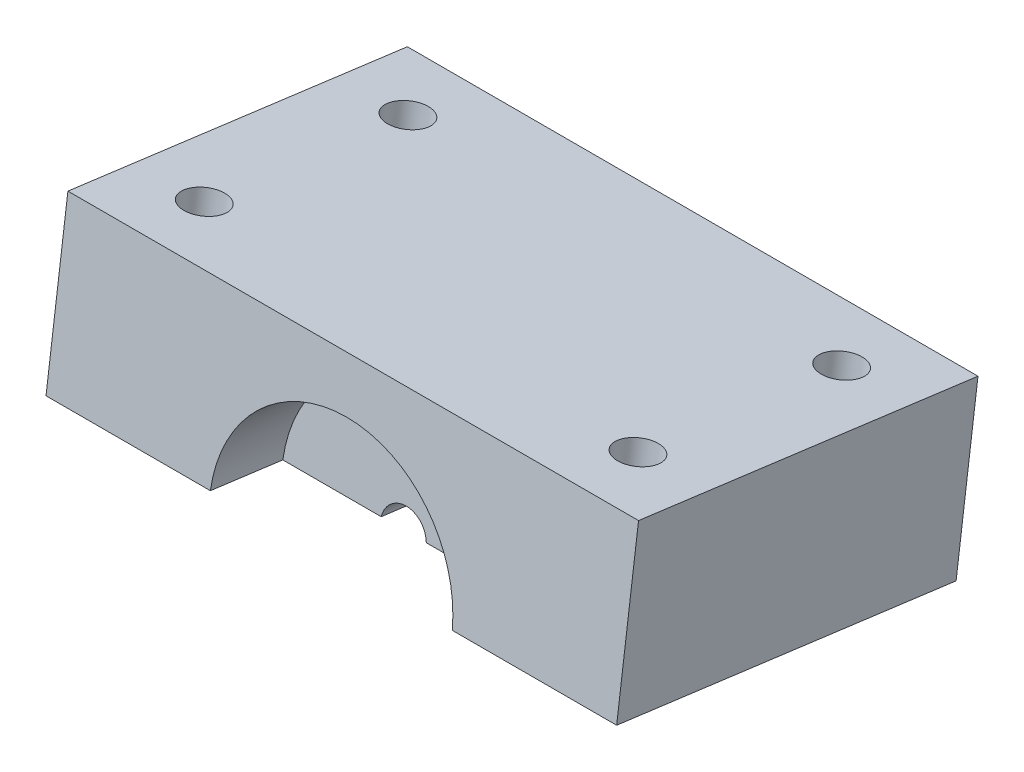
SolidWorks part; units mm, degrees
ref_plane "Front Plane" through (0, 0, 0) normal (0, 0, 1) x (1, 0, 0)
ref_plane "Top Plane" through (0, 0, 0) normal (0, 1, 0) x (1, 0, 0)
ref_plane "Right Plane" through (0, 0, 0) normal (1, 0, 0) x (0, 0, -1)
ref_axis "Axis1" through (-88.99, 0, 0) along (1, 0, 0)
ref_plane "7.5deg Ref" through (0, 0, 0) normal (0, 0.1305, 0.9914) x (1, 0, 0)
sketch "Sketch1" plane through (0, 0, 0) normal (0, 0.1305, 0.9914) x (1, 0, 0)
  line L1 (62.5, 0.75) -> (62.5, 37.5)
  line L2 (62.5, 37.5) -> (-62.5, 37.5)
  line L3 (-62.5, 37.5) -> (-62.5, 0.75)
  line L4 (-62.5, 0.75) -> (-26.4894, 0.75)
  line L5 (26.4894, 0.75) -> (62.5, 0.75)
  line L6 (0, 0) -> (0, 37.5) construction
  arc A0 (26.4894, 0.75) -> (-26.4894, 0.75) centre (0, 0) ccw
  dimension "D3" = 53
  dimension "D1" = 125
  dimension "D2" = 36.75
  dimension "D4" = 0.75
extrude "Extrude Top Block" add sketch "Sketch1" against normal blind 75
sketch "Sketch2" plane through (0, 37.1792, -4.8947) normal (0, 0.9914, -0.1305) x (1, 0, 0)
  line L0 (0, 75.0939) -> (0, -22.75) construction
  line L1 (0, -25.4238) -> (0, 25.4238) construction
  line L2 (-72.1929, 37.5) -> (74.8374, 37.5) construction
  line L3 (-47.5, 59.9553) -> (-47.5, 15) construction
  line L4 (-62.5, 75) -> (-62.5, 0) construction
  line L5 (-59.8697, 0) -> (59.8697, 0) construction
  circle A0 centre (-47.5, 15) radius 2.75
  circle A1 centre (-47.5, 60) radius 2.75
  circle A2 centre (47.5, 15) radius 2.75
  circle A3 centre (47.5, 60) radius 2.75
  dimension "D3" = 5.5
  dimension "D1" = 15
  dimension "D2" = 15
  dimension "D4" = 37.5
extrude "Cut-Extrude Bolt Pattern" cut sketch "Sketch2" against normal through all both and the other way through all
sketch "Sketch4" plane through (0, 0, 0) normal (0, 0.1305, 0.9914) x (1, 0, 0)
  line L0 (-26.4894, 0.75) -> (26.4894, 0.75)
  arc A0 (26.4894, 0.75) -> (-26.4894, 0.75) centre (0, 0) ccw
  arc A1 (26.4894, 0.75) -> (-26.4894, 0.75) centre (0, 0) ccw construction
extrude "Extrude Addition Material" add sketch "Sketch4" along direction (0, 0.1305, 0.9914) on the side against the normal up to surface (75 mm away) from offset 16 up to face at (0, 7.3543, -76.6154) offset against normal yes
sketch "Sketch3" plane through (0, 0, 0) normal (1, 0, 0) x (0, 0, -1)
  line L0 (0, 0) -> (74.2659, -9.7773) construction
  line L1 (21.9059, 43.8111) -> (14.9673, -8.8927) construction
  line L2 (41.4977, 1.0928) -> (61.3266, -1.5177)
  line L3 (74.4563, -9.0459) -> (0.0979, 0.7436) construction
  line L13 (61.3266, -1.5177) -> (60.4781, -7.9621)
  line L14 (60.4781, -7.9621) -> (40.6492, -5.3516)
  line L15 (40.6492, -5.3516) -> (41.4977, 1.0928)
  line L16 (74.4563, -9.0459) -> (79.2531, 27.3897) construction
  line L17 (40.6492, -5.3516) -> (46.6434, 40.1787) construction
  line L18 (7.8146, 59.3575) -> (-7.8146, -59.3575) construction
  dimension "D1" = 0.75
  dimension "D2" = 20
  dimension "D6" = 6.5
  dimension "D7" = 16
  dimension "D8" = 25
revolve "Cut-Extrude Seat for Linear Bearing" cut sketch "Sketch3" angle 360 about L0
sketch "Sketch6" plane through (0, -2.0884, -15.8631) normal (0, 0.1305, 0.9914) x (1, 0, 0)
  line L1 (-4.9434, 0.75) -> (4.9434, 0.75)
  line L3 (-26.4894, 0.75) -> (26.4894, 0.75) construction
  arc A0 (4.9434, 0.75) -> (-4.9434, 0.75) centre (0, 0) ccw
  arc A1 (26.4894, 0.75) -> (-26.4894, 0.75) centre (0, 0) ccw construction
  dimension "D1" = 10
extrude "Cut-Extrude Shaft Pathway" cut sketch "Sketch6" against normal up to surface (59 mm away) up to face at (0, 9.1719, -76.8547)
sketch "Sketch7" plane through (0, -9.7895, -74.3584) normal (0, -0.1305, -0.9914) x (-1, 0, 0)
  line L0 (0, 66.1064) -> (0, -24.2487) construction
  line L1 (0, 25.4238) -> (0, -25.4238) construction
  line L2 (-20, 20) -> (20, 20) construction
  circle A0 centre (-20, 20) radius 2
  circle A1 centre (20, 20) radius 2
  dimension "D4" = 4
  dimension "D5" = 4
  dimension "D1" = 20
  dimension "D2" = 20
  dimension "D3" = 20
extrude "Cut-Extrude1" cut sketch "Sketch7" against normal blind 25
sketch "Sketch8" plane through (0, 37.1792, -4.8947) normal (0, 0.9914, -0.1305) x (1, 0, 0)
  circle A0 centre (47.5, 15) radius 4.5
  circle A1 centre (47.5, 60) radius 4.5
  circle A2 centre (-47.5, 15) radius 4.5
  circle A3 centre (-47.5, 60) radius 4.5
  dimension "D1" = 9
extrude "Cut-Extrude2" cut sketch "Sketch8" against normal blind 6
